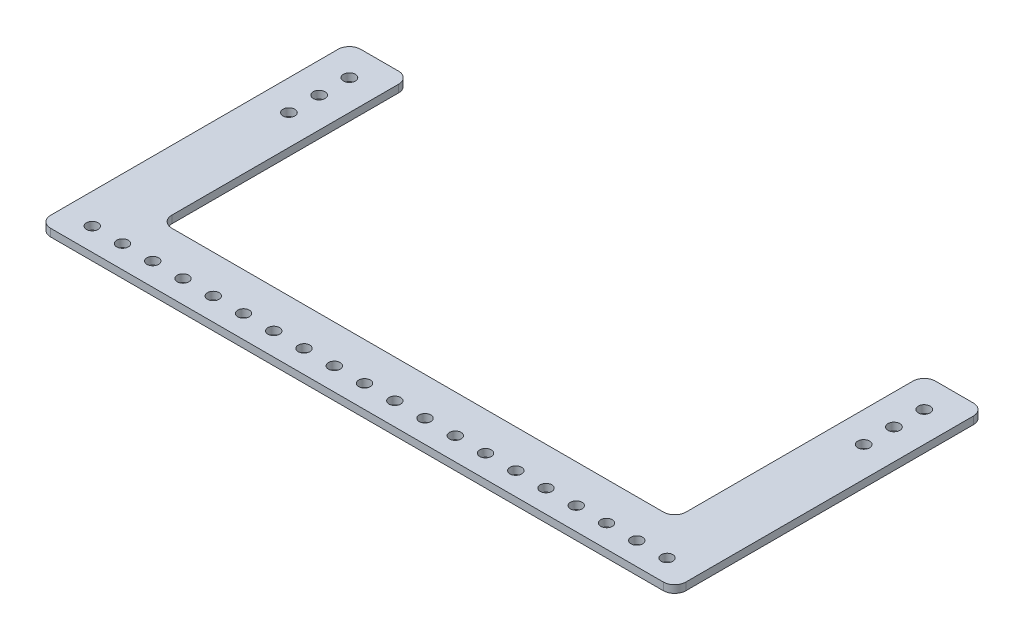
SolidWorks part; units mm, degrees
material "6061-T6 (SS)"
ref_plane "Front Plane" through (0, 0, 0) normal (0, 0, 1) x (1, 0, 0)
ref_plane "Top Plane" through (0, 0, 0) normal (0, 1, 0) x (1, 0, 0)
ref_plane "Right Plane" through (0, 0, 0) normal (1, 0, 0) x (0, 0, -1)
sketch "Sketch2" plane through (0, 0, 0) normal (0, 1, 0) x (1, 0, 0)
  line L0 (0, 65.0875) -> (0, -65.0875) construction
  line L1 (-133.35, -65.0875) -> (133.35, -65.0875)
  line L2 (-133.35, -65.0875) -> (-133.35, 65.0875)
  line L3 (-133.35, 65.0875) -> (133.35, 65.0875)
  line L4 (133.35, -65.0875) -> (133.35, 65.0875)
  line L5 (-133.35, -65.0875) -> (133.35, 65.0875) construction
  line L6 (-133.35, 65.0875) -> (133.35, -65.0875) construction
  line L7 (-107.95, 65.0875) -> (107.95, 65.0875)
  line L8 (-107.95, 65.0875) -> (-107.95, -39.624)
  line L9 (-107.95, -39.624) -> (107.95, -39.624)
  line L10 (107.95, 65.0875) -> (107.95, -39.624)
  line L11 (133.35, 65.0875) -> (107.95, 65.0875) construction
  line L12 (133.35, 65.0875) -> (133.35, -39.624) construction
  line L13 (133.35, -39.624) -> (107.95, -39.624) construction
  line L14 (107.95, 65.0875) -> (107.95, -39.624) construction
  circle A0 centre (-120.65, 52.3875) radius 2.4892
  circle A1 centre (-120.65, 39.6875) radius 2.4892
  circle A2 centre (-120.65, 26.9875) radius 2.4892
  circle A6 centre (120.65, 26.9875) radius 2.4892
  circle A7 centre (120.65, 39.6875) radius 2.4892
  circle A8 centre (120.65, 52.3875) radius 2.4892
  point P0 (0, 0)
  point P10 (0, -39.624)
  point P11 (0, -65.0875)
  dimension "D8" = 4.9784
  dimension "D1" = 266.7
  dimension "D2" = 130.175
  dimension "D3" = 215.9
  dimension "D4" = 25.4635
  dimension "D5" = 12.7
  dimension "D6" = 12.7
  dimension "D7" = 12.7
  dimension "D9" = 12.7
  dimension "D10" = 12.7
  dimension "D11" = 12.7
extrude "Boss-Extrude1" add sketch "Sketch2" along normal blind 3.175 contours L3 L10 L9 L8 L2 L1 L4 A7 A0 A1 A2 A6 A8 region at (-130.3823, 0, 0)
fillet "Fillet1" radius 4.7625 8 edges at (133.35, 1.5875, -65.0875) (-133.35, 1.5875, 65.0875) (-133.35, 1.5875, -65.0875) (-107.95, 1.5875, -65.0875) (-107.95, 1.5875, 39.624) (107.95, 1.5875, 39.624) (107.95, 1.5875, -65.0875) (133.35, 1.5875, 65.0875)
sketch "Sketch3" plane through (0, 3.175, 0) normal (0, 1, 0) x (1, 0, 0)
  line L0 (-133.35, -60.325) -> (-133.35, 60.325) construction
  line L1 (-128.5875, -65.0875) -> (128.5875, -65.0875) construction
  line L2 (0, -39.624) -> (0, -65.0875) construction
  line L3 (-103.1875, -39.624) -> (103.1875, -39.624) construction
  circle A0 centre (-120.65, -55.5625) radius 2.4384
  circle A19 centre (-107.95, -55.5625) radius 2.4384
  circle A20 centre (-95.25, -55.5625) radius 2.4384
  circle A21 centre (-82.55, -55.5625) radius 2.4384
  circle A22 centre (-69.85, -55.5625) radius 2.4384
  circle A23 centre (-57.15, -55.5625) radius 2.4384
  circle A24 centre (-44.45, -55.5625) radius 2.4384
  circle A25 centre (-31.75, -55.5625) radius 2.4384
  circle A26 centre (-19.05, -55.5625) radius 2.4384
  circle A27 centre (-6.35, -55.5625) radius 2.4384
  circle A28 centre (6.35, -55.5625) radius 2.4384
  circle A29 centre (19.05, -55.5625) radius 2.4384
  circle A30 centre (31.75, -55.5625) radius 2.4384
  circle A31 centre (44.45, -55.5625) radius 2.4384
  circle A32 centre (57.15, -55.5625) radius 2.4384
  circle A33 centre (69.85, -55.5625) radius 2.4384
  circle A34 centre (82.55, -55.5625) radius 2.4384
  circle A35 centre (95.25, -55.5625) radius 2.4384
  circle A36 centre (107.95, -55.5625) radius 2.4384
  circle A37 centre (120.65, -55.5625) radius 2.4384
  dimension "D1" = 4.8768
  dimension "D5" = 12.7
  dimension "D2" = 12.7
  dimension "D3" = 9.525
  dimension "D4" = 20
extrude "Cut-Extrude1" cut sketch "Sketch3" against normal through all
